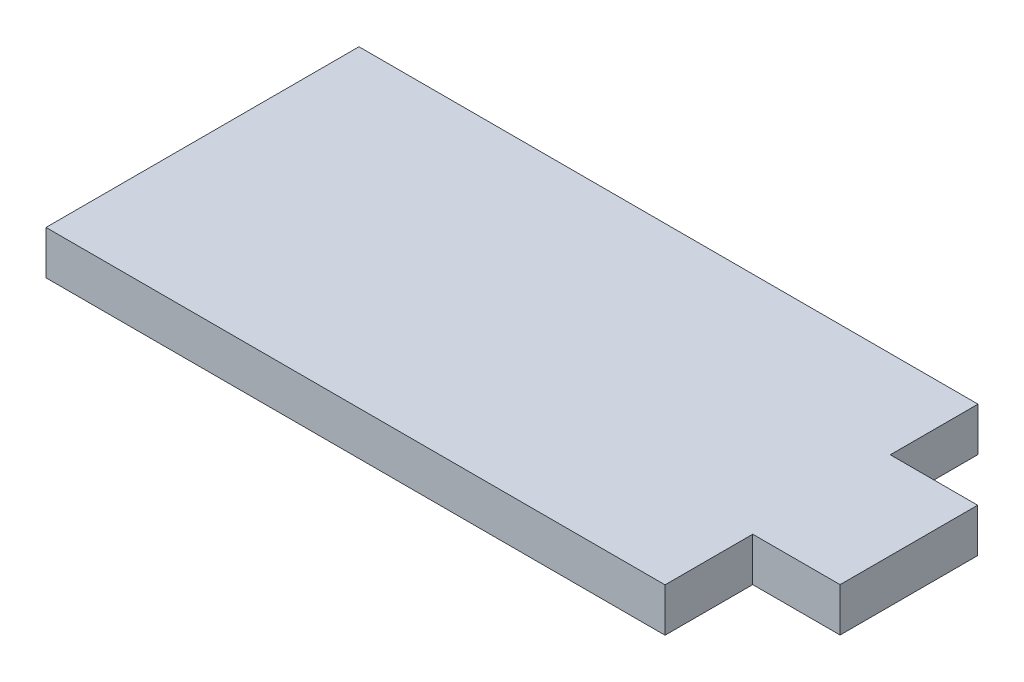
SolidWorks part; units mm, degrees
material "Cedar"
ref_plane "Front Plane" through (0, 0, 0) normal (0, 0, 1) x (1, 0, 0)
ref_plane "Top Plane" through (0, 0, 0) normal (0, 1, 0) x (1, 0, 0)
ref_plane "Right Plane" through (0, 0, 0) normal (1, 0, 0) x (0, 0, -1)
sketch "Sketch1" plane through (0, 0, 0) normal (0, 1, 0) x (1, 0, 0)
  line L0 (-22.5, 6.375) -> (22.5, 6.375)
  line L1 (22.5, 6.375) -> (22.5, 0)
  line L2 (22.5, 0) -> (28.85, 0)
  line L3 (28.85, 0) -> (28.85, -10)
  line L4 (28.85, -10) -> (22.5, -10)
  line L5 (22.5, -10) -> (22.5, -16.375)
  line L6 (22.5, -16.375) -> (-22.5, -16.375)
  line L7 (-22.5, -16.375) -> (-22.5, -10)
  line L8 (-22.5, -10) -> (-28.85, -10)
  line L9 (-28.85, -10) -> (-28.85, 0)
  line L10 (-28.85, 0) -> (-22.5, 0)
  line L11 (-22.5, 0) -> (-22.5, 6.375)
  line L12 (-22.5, 0) -> (-22.5, -10) construction
  point P11 (0, 6.375)
  point P14 (-28.85, -5)
  dimension "D1" = 6.35
  dimension "D2" = 10
  dimension "D3" = 45
  dimension "D4" = 22.75
extrude "Boss-Extrude1" add sketch "Sketch1" along normal blind 3.175 contours L11 L12 L7 L6 L5 L4 L3 L2 L1 L0 region at (1.4995, 0, 5)
sketch "Sketch2" plane through (0, 3.175, 0) normal (0, 1, 0) x (1, 0, 0)
  line L8 (-22.5, 6.375) -> (-22.5, -16.375)
  line L9 (-22.5, -16.375) -> (22.5, -16.375)
  line L10 (22.5, -16.375) -> (22.5, -10)
  line L11 (22.5, -10) -> (28.85, -10)
  line L12 (28.85, -10) -> (28.85, 0)
  line L13 (28.85, 0) -> (22.5, 0)
  line L14 (22.5, 0) -> (22.5, 6.375)
  line L15 (22.5, 6.375) -> (-22.5, 6.375)
  line L16 (-22.5, 6.375) -> (-22.5, -16.375)
  line L17 (-22.5, -16.375) -> (22.5, -16.375)
  line L18 (22.5, -16.375) -> (22.5, -10)
  line L19 (22.5, -10) -> (28.85, -10)
  line L20 (28.85, -10) -> (28.85, 0)
  line L21 (28.85, 0) -> (22.5, 0)
  line L22 (22.5, 0) -> (22.5, 6.375)
  line L23 (22.5, 6.375) -> (-22.5, 6.375)
  dimension "D1" = 0
equation "\"length\"= 22.75mm"
equation "\"w_mach\"= 45mm"
equation "\"w_tab\"= 10mm"
equation "\"t_wood\"= 0.125in"
equation "\"t_side\"= 0.25in"
equation "\"D1@Sketch1\"=\"t_side\""
equation "\"D2@Sketch1\"=\"w_tab\""
equation "\"D3@Sketch1\"=\"w_mach\""
equation "\"D4@Sketch1\"=\"length\""
equation "\"D1@Boss-Extrude1\"=\"t_wood\""
